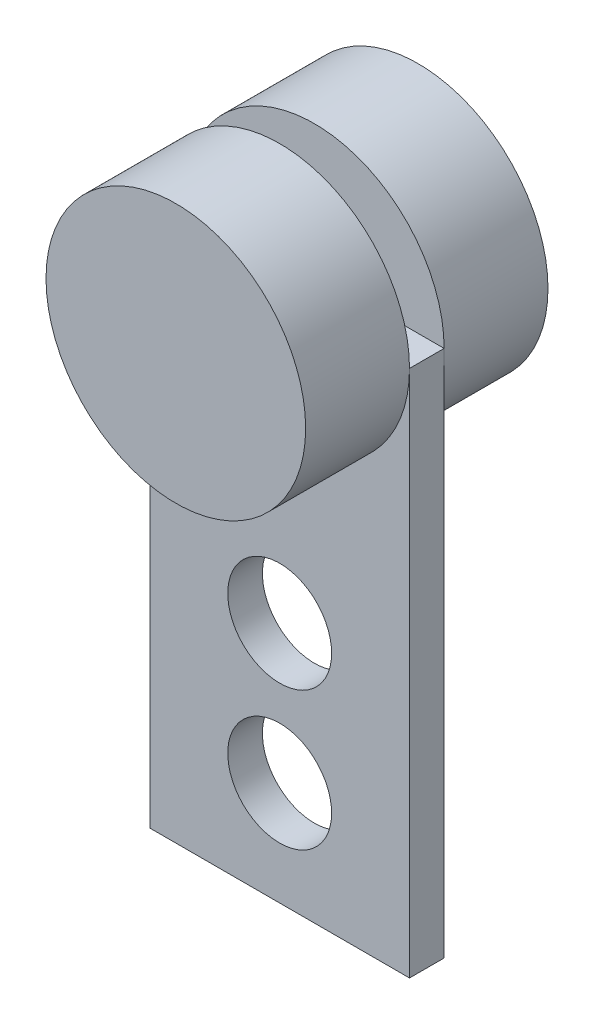
SolidWorks part; units mm, degrees
ref_plane "Płaszczyzna przednia" through (0, 0, 0) normal (0, 0, 1) x (1, 0, 0)
ref_plane "Płaszczyzna górna" through (0, 0, 0) normal (0, 1, 0) x (1, 0, 0)
ref_plane "Płaszczyzna prawa" through (0, 0, 0) normal (1, 0, 0) x (0, 0, -1)
sketch "Szkic1" plane through (0, 0, 0) normal (0, 0, 1) x (1, 0, 0)
  line L1 (-7.5, -15.25) -> (7.5, -15.25)
  line L2 (-7.5, -15.25) -> (-7.5, 15.25)
  line L3 (-7.5, 15.25) -> (7.5, 15.25)
  line L4 (7.5, -15.25) -> (7.5, 15.25)
  line L5 (0, 15.25) -> (0, -15.25) construction
  line L6 (-7.5, 0) -> (7.5, 0) construction
  circle A0 centre (0, -9.25) radius 3
  circle A1 centre (0, -1.25) radius 3
  point P0 (0, 0)
  dimension "D3" = 6
  dimension "D4" = 6
  dimension "D5" = 14
  dimension "D1" = 15
  dimension "D2" = 30.5
extrude "Dodanie-wyciągnięcie1" add sketch "Szkic1" along normal blind 2
sketch "Szkic2" plane through (0, 0, 2) normal (0, 0, 1) x (1, 0, 0)
  line L0 (7.5, 15.25) -> (-7.5, 15.25) construction
  circle A0 centre (0, 15.25) radius 7.5
  dimension "D1" = 15
extrude "Dodanie-wyciągnięcie2" add sketch "Szkic2" along normal blind 6
extrude "Dodanie-wyciągnięcie3" add sketch "Szkic2<2>" against normal blind 6 from surface starting at face at (3, -9.25, 0)
sketch "Szkic2<2>" plane through (0, 0, 2) normal (0, 0, 1) x (1, 0, 0) same geometry as "Szkic2"
